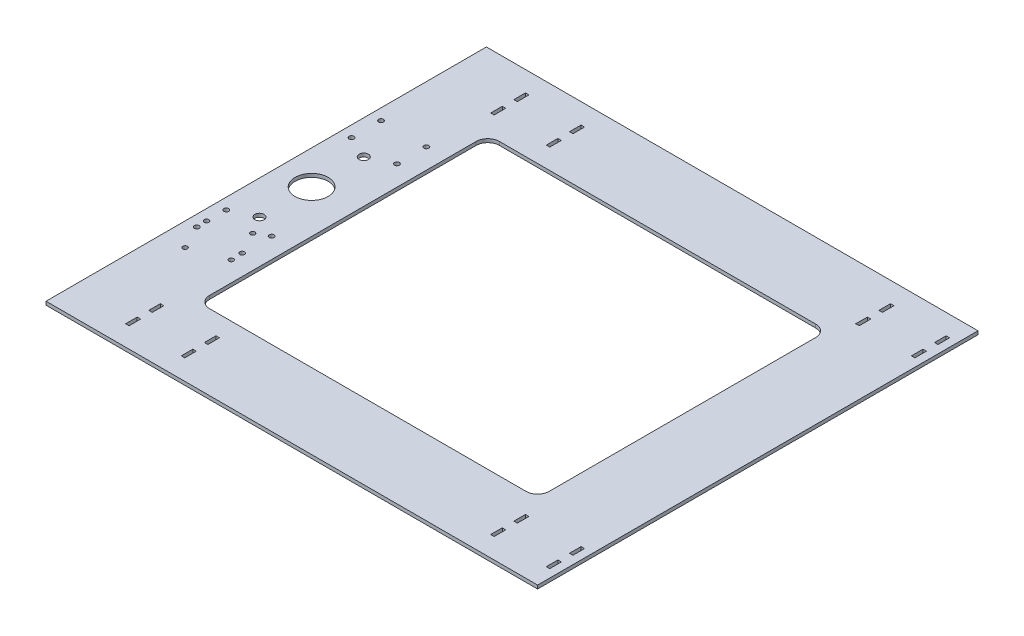
SolidWorks part; units mm, degrees
material "PC High Viscosity"
ref_plane "Front Plane" through (0, 0, 0) normal (0, 0, 1) x (1, 0, 0)
ref_plane "Top Plane" through (0, 0, 0) normal (0, 1, 0) x (1, 0, 0)
ref_plane "Right Plane" through (0, 0, 0) normal (1, 0, 0) x (0, 0, -1)
sketch "Sketch1" plane through (0, 0, 0) normal (0, 1, 0) x (1, 0, 0)
  line L1 (212.09, -190) -> (-212.09, -190)
  line L2 (212.09, -190) -> (212.09, 190)
  line L3 (212.09, 190) -> (-212.09, 190)
  line L4 (-212.09, -190) -> (-212.09, 190)
  line L5 (212.09, -190) -> (-212.09, 190) construction
  line L6 (212.09, 190) -> (-212.09, -190) construction
  point P0 (0, 0)
  dimension "D1" = 424.18
  dimension "D2" = 380
extrude "Boss-Extrude1" add sketch "Sketch1" along normal blind 3
sketch "Sketch2" plane through (0, 3, 0) normal (0, 1, 0) x (1, 0, 0)
  line L0 (212.09, 0) -> (-212.09, 0) construction
  line L1 (212.09, -190) -> (212.09, 190) construction
  line L2 (-212.09, 190) -> (-212.09, -190) construction
  line L4 (-102.91, -125) -> (147.09, -125)
  line L5 (-102.91, -125) -> (-102.91, 125)
  line L6 (-102.91, 125) -> (147.09, 125)
  line L7 (147.09, -125) -> (147.09, 125)
  line L8 (-102.91, -125) -> (147.09, 125) construction
  line L9 (-102.91, 125) -> (147.09, -125) construction
  line L10 (147.09, 125) -> (212.09, 125) construction
  line L11 (147.09, 125) -> (147.09, 190) construction
  line L12 (147.09, 190) -> (212.09, 190) construction
  line L13 (212.09, 125) -> (212.09, 190) construction
  point P6 (22.09, 0)
  dimension "D1" = 250
  dimension "D2" = 250
extrude "Cut-Extrude1" cut sketch "Sketch2" against normal through all
sketch "Sketch3" plane through (0, 3, 0) normal (0, 1, 0) x (1, 0, 0)
  line L0 (155.59, -152.5) -> (155.59, -162.5) construction
  line L1 (154.09, -152.5) -> (157.09, -152.5)
  line L2 (154.09, -152.5) -> (154.09, -142.5)
  line L3 (154.09, -142.5) -> (157.09, -142.5)
  line L4 (157.09, -152.5) -> (157.09, -142.5)
  line L5 (154.09, -152.5) -> (157.09, -142.5) construction
  line L6 (154.09, -142.5) -> (157.09, -152.5) construction
  line L7 (154.09, -172.5) -> (157.09, -172.5)
  line L8 (154.09, -172.5) -> (154.09, -162.5)
  line L9 (154.09, -162.5) -> (157.09, -162.5)
  line L10 (157.09, -172.5) -> (157.09, -162.5)
  line L11 (154.09, -172.5) -> (157.09, -162.5) construction
  line L12 (154.09, -162.5) -> (157.09, -172.5) construction
  line L13 (205.09, -152.5) -> (202.09, -152.5)
  line L14 (205.09, -152.5) -> (205.09, -142.5)
  line L15 (205.09, -142.5) -> (202.09, -142.5)
  line L16 (202.09, -152.5) -> (202.09, -142.5)
  line L17 (205.09, -152.5) -> (202.09, -142.5) construction
  line L18 (205.09, -142.5) -> (202.09, -152.5) construction
  line L19 (205.09, -172.5) -> (202.09, -172.5)
  line L20 (205.09, -172.5) -> (205.09, -162.5)
  line L21 (205.09, -162.5) -> (202.09, -162.5)
  line L22 (202.09, -172.5) -> (202.09, -162.5)
  line L23 (205.09, -172.5) -> (202.09, -162.5) construction
  line L24 (205.09, -162.5) -> (202.09, -172.5) construction
  line L25 (155.59, -167.5) -> (203.59, -167.5) construction
  line L26 (155.59, -167.5) -> (155.59, -147.5) construction
  line L27 (155.59, -147.5) -> (203.59, -147.5) construction
  line L28 (203.59, -167.5) -> (203.59, -147.5) construction
  line L29 (155.59, -167.5) -> (203.59, -147.5) construction
  line L30 (155.59, -147.5) -> (203.59, -167.5) construction
  line L31 (22.09, 125) -> (22.09, -125) construction
  line L32 (-135.41, 157.5) -> (179.59, 157.5) construction
  line L33 (-135.41, 157.5) -> (-135.41, -157.5) construction
  line L34 (-135.41, -157.5) -> (179.59, -157.5) construction
  line L35 (179.59, 157.5) -> (179.59, -157.5) construction
  line L36 (-135.41, 157.5) -> (179.59, -157.5) construction
  line L37 (-135.41, -157.5) -> (179.59, 157.5) construction
  line L38 (147.09, 125) -> (-102.91, 125) construction
  line L39 (-102.91, -125) -> (147.09, -125) construction
  line L40 (179.59, 0) -> (-135.41, 0) construction
  line L41 (-160.91, -142.5) -> (-157.91, -152.5) construction
  line L42 (-160.91, -152.5) -> (-157.91, -142.5) construction
  line L43 (-157.91, -152.5) -> (-157.91, -142.5)
  line L44 (-160.91, -142.5) -> (-157.91, -142.5)
  line L45 (-160.91, -152.5) -> (-160.91, -142.5)
  line L46 (-160.91, -152.5) -> (-157.91, -152.5)
  line L47 (-160.91, -162.5) -> (-157.91, -172.5) construction
  line L48 (-160.91, -172.5) -> (-157.91, -162.5) construction
  line L49 (-157.91, -172.5) -> (-157.91, -162.5)
  line L50 (-160.91, -162.5) -> (-157.91, -162.5)
  line L51 (-160.91, -172.5) -> (-160.91, -162.5)
  line L52 (-160.91, -172.5) -> (-157.91, -172.5)
  line L53 (-109.91, -162.5) -> (-112.91, -172.5) construction
  line L54 (-109.91, -172.5) -> (-112.91, -162.5) construction
  line L55 (-112.91, -172.5) -> (-112.91, -162.5)
  line L56 (-109.91, -162.5) -> (-112.91, -162.5)
  line L57 (-109.91, -172.5) -> (-109.91, -162.5)
  line L58 (-109.91, -172.5) -> (-112.91, -172.5)
  line L59 (-109.91, -142.5) -> (-112.91, -152.5) construction
  line L60 (-109.91, -152.5) -> (-112.91, -142.5) construction
  line L61 (-112.91, -152.5) -> (-112.91, -142.5)
  line L62 (-109.91, -142.5) -> (-112.91, -142.5)
  line L63 (-109.91, -152.5) -> (-109.91, -142.5)
  line L64 (-109.91, -152.5) -> (-112.91, -152.5)
  line L65 (205.09, 142.5) -> (202.09, 152.5) construction
  line L66 (205.09, 152.5) -> (202.09, 142.5) construction
  line L67 (202.09, 152.5) -> (202.09, 142.5)
  line L68 (205.09, 142.5) -> (202.09, 142.5)
  line L69 (205.09, 152.5) -> (205.09, 142.5)
  line L70 (205.09, 152.5) -> (202.09, 152.5)
  line L71 (205.09, 162.5) -> (202.09, 172.5) construction
  line L72 (205.09, 172.5) -> (202.09, 162.5) construction
  line L73 (202.09, 172.5) -> (202.09, 162.5)
  line L74 (205.09, 162.5) -> (202.09, 162.5)
  line L75 (205.09, 172.5) -> (205.09, 162.5)
  line L76 (205.09, 172.5) -> (202.09, 172.5)
  line L77 (154.09, 162.5) -> (157.09, 172.5) construction
  line L78 (154.09, 172.5) -> (157.09, 162.5) construction
  line L79 (157.09, 172.5) -> (157.09, 162.5)
  line L80 (154.09, 162.5) -> (157.09, 162.5)
  line L81 (154.09, 172.5) -> (154.09, 162.5)
  line L82 (154.09, 172.5) -> (157.09, 172.5)
  line L83 (154.09, 142.5) -> (157.09, 152.5) construction
  line L84 (154.09, 152.5) -> (157.09, 142.5) construction
  line L85 (157.09, 152.5) -> (157.09, 142.5)
  line L86 (154.09, 142.5) -> (157.09, 142.5)
  line L87 (154.09, 152.5) -> (154.09, 142.5)
  line L88 (154.09, 152.5) -> (157.09, 152.5)
  line L89 (-135.41, -157.5) -> (179.59, 157.5) construction
  line L90 (-109.91, 152.5) -> (-112.91, 142.5) construction
  line L91 (-109.91, 142.5) -> (-112.91, 152.5) construction
  line L92 (-109.91, 172.5) -> (-112.91, 162.5) construction
  line L93 (-109.91, 162.5) -> (-112.91, 172.5) construction
  line L94 (-109.91, 152.5) -> (-112.91, 152.5)
  line L95 (-109.91, 152.5) -> (-109.91, 142.5)
  line L96 (-109.91, 142.5) -> (-112.91, 142.5)
  line L97 (-112.91, 152.5) -> (-112.91, 142.5)
  line L98 (-109.91, 172.5) -> (-112.91, 172.5)
  line L99 (-109.91, 172.5) -> (-109.91, 162.5)
  line L100 (-109.91, 162.5) -> (-112.91, 162.5)
  line L101 (-112.91, 172.5) -> (-112.91, 162.5)
  line L102 (-160.91, 172.5) -> (-157.91, 162.5) construction
  line L103 (-160.91, 162.5) -> (-157.91, 172.5) construction
  line L104 (-160.91, 152.5) -> (-157.91, 142.5) construction
  line L105 (-160.91, 142.5) -> (-157.91, 152.5) construction
  line L106 (-160.91, 172.5) -> (-157.91, 172.5)
  line L107 (-160.91, 172.5) -> (-160.91, 162.5)
  line L108 (-160.91, 162.5) -> (-157.91, 162.5)
  line L109 (-157.91, 172.5) -> (-157.91, 162.5)
  line L110 (-160.91, 152.5) -> (-157.91, 152.5)
  line L111 (-160.91, 152.5) -> (-160.91, 142.5)
  line L112 (-160.91, 142.5) -> (-157.91, 142.5)
  line L113 (-157.91, 152.5) -> (-157.91, 142.5)
  line L114 (-212.09, -190) -> (212.09, -190) construction
  line L115 (147.09, -125) -> (147.09, 125) construction
  point P0 (155.59, -147.5)
  point P5 (155.59, -167.5)
  point P10 (203.59, -147.5)
  point P15 (203.59, -167.5)
  point P20 (179.59, -157.5)
  point P27 (22.09, 0)
  point P44 (-159.41, -147.5)
  point P49 (-159.41, -167.5)
  point P54 (-111.41, -167.5)
  point P59 (-111.41, -147.5)
  point P64 (203.59, 147.5)
  point P69 (203.59, 167.5)
  point P74 (155.59, 167.5)
  point P79 (155.59, 147.5)
  point P88 (-111.41, 147.5)
  point P89 (-111.41, 167.5)
  point P98 (-159.41, 167.5)
  point P99 (-159.41, 147.5)
  dimension "D1" = 3
  dimension "D2" = 45
  dimension "D3" = 10
  dimension "D4" = 32.5
  dimension "D5" = 32.5
extrude "Cut-Extrude2" cut sketch "Sketch3" against normal through all
sketch "Sketch6" plane through (0, 3, 0) normal (0, 1, 0) x (1, 0, 0)
  line L0 (-202.475, 10) -> (-163.345, 10) construction
  line L1 (-102.91, 125) -> (-102.91, -125) construction
  line L2 (-163.345, -44.0505) -> (-202.475, -44.0505) construction
  line L3 (-173.6822, -50.1326) -> (-163.0266, -79.2438) construction
  line L4 (-173.6822, -50.1326) -> (-202.7934, -60.7882) construction
  line L5 (-202.7934, -60.7882) -> (-192.1378, -89.8994) construction
  line L6 (-163.0266, -79.2438) -> (-192.1378, -89.8994) construction
  line L7 (-173.6822, -50.1326) -> (-192.1378, -89.8994) construction
  line L8 (-202.7934, -60.7882) -> (-163.0266, -79.2438) construction
  line L9 (-163.345, -44.0505) -> (-163.345, 64.0505) construction
  line L10 (-163.345, 64.0505) -> (-202.475, 64.0505) construction
  line L11 (-202.475, -44.0505) -> (-202.475, 64.0505) construction
  line L12 (-163.345, -44.0505) -> (-202.475, 64.0505) construction
  line L13 (-163.345, 64.0505) -> (-202.475, -44.0505) construction
  line L14 (-202.475, 64.0505) -> (-163.345, 64.0505) construction
  line L15 (-202.475, 64.0505) -> (-202.475, 89.4505) construction
  line L16 (-202.475, 89.4505) -> (-163.345, 89.4505) construction
  line L17 (-163.345, 64.0505) -> (-163.345, 89.4505) construction
  line L18 (-212.09, 10) -> (-102.91, 10) construction
  line L20 (-212.09, 190) -> (-212.09, -190) construction
  line L21 (-102.91, 125) -> (-102.91, -125) construction
  circle A0 centre (-182.91, 10) radius 14.2875
  circle A1 centre (-202.7934, -60.7882) radius 2
  circle A2 centre (-192.1378, -89.8994) radius 2
  circle A3 centre (-163.0266, -79.2438) radius 2
  circle A4 centre (-173.6822, -50.1326) radius 2
  circle A5 centre (-163.345, 64.0505) radius 2.0833
  circle A6 centre (-202.475, 64.0505) radius 2.0833
  circle A7 centre (-202.475, -44.0505) radius 2.0833
  circle A8 centre (-163.345, -44.0505) radius 2.0833
  circle A9 centre (-202.475, 89.4505) radius 2.0833
  circle A10 centre (-163.345, 89.4505) radius 2.0833
  circle A11 centre (-163.345, -69.4505) radius 2.0833
  circle A12 centre (-202.475, -69.4505) radius 2.0833
  circle A13 centre (-182.91, -35) radius 4
  circle A14 centre (-182.91, 55) radius 4
  point P6 (-182.91, -70.016)
  point P42 (0, 0)
  dimension "D1" = 28.575
  dimension "D2" = 80
  dimension "D3" = 4
  dimension "D9" = 4.1667
  dimension "D11" = 8
  dimension "D12" = 90
  dimension "D4" = 31
  dimension "D5" = 80.016
  dimension "D6" = 10
  dimension "D7" = 108.101
  dimension "D8" = 39.13
  dimension "D10" = 25.4
extrude "Cut-Extrude3" cut sketch "Sketch6" against normal through all
sketch "Sketch7" plane through (0, 3, 0) normal (0, 1, 0) x (1, 0, 0)
  line L0 (-102.91, -125) -> (147.09, -125) construction
  line L1 (-57.5273, -125) -> (-145.8924, -125)
  line L2 (-57.5273, -125) -> (-57.5273, 125)
  line L3 (-57.5273, 125) -> (-145.8924, 125)
  line L4 (-145.8924, -125) -> (-145.8924, 125)
  line L5 (147.09, 125) -> (-102.91, 125) construction
extrude "Cut-Extrude4" cut sketch "Sketch7" against normal through all
fillet "Fillet1" radius 10 4 edges at (147.09, 1.5, 125) (147.09, 1.5, -125) (-145.8924, 1.5, 125) (-145.8924, 1.5, -125)
equation "\"case_width\"= 16.7in"
equation "\"case_depth\"= 12.6in"
equation "\"D1@Sketch1\"=\"case_width\""
equation "\"pulley_pitch_diam\"= 12.73mm"
equation "\"pulley_total_width\"= 16mm"
equation "\"pulley_total_diam\"= 16mm"
equation "\"belt_width\"= 6mm"
equation "\"material_thickness\"= 3mm"
equation "\"shaft_diam\"= 8mm"
equation "\"bearing_od\"= 22mm"
equation "\"bearing_thickness\"= 7mm"
